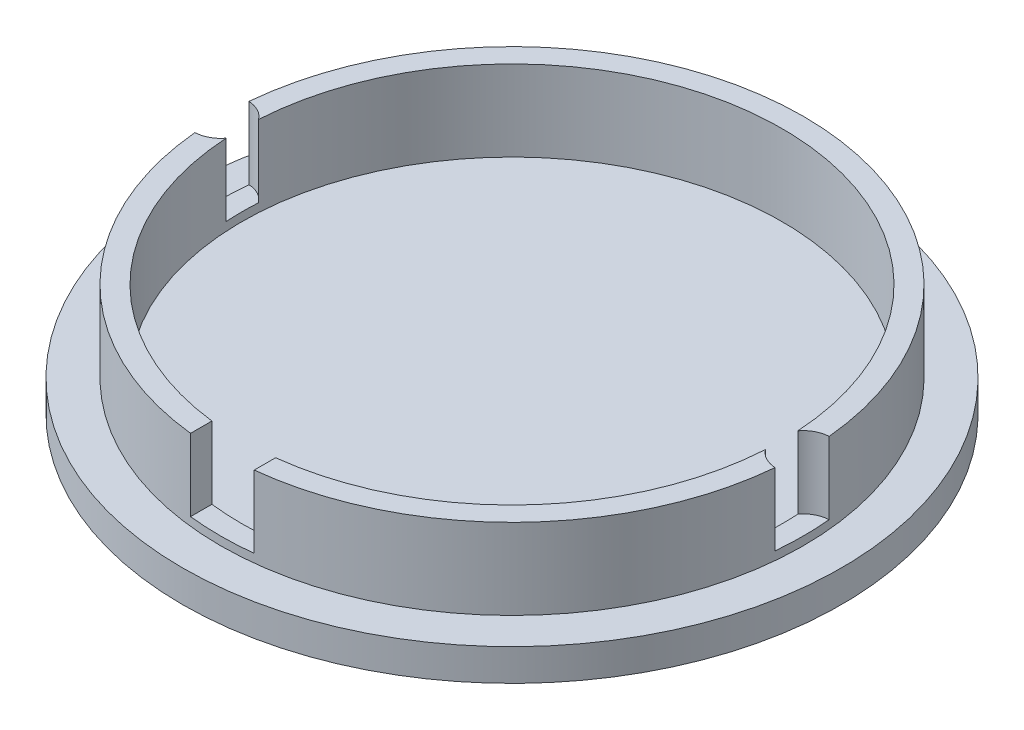
SolidWorks part; units mm, degrees
ref_plane "Front Plane" through (0, 0, 0) normal (0, 0, 1) x (1, 0, 0)
ref_plane "Top Plane" through (0, 0, 0) normal (0, 1, 0) x (1, 0, 0)
ref_plane "Right Plane" through (0, 0, 0) normal (1, 0, 0) x (0, 0, -1)
sketch "Sketch1" plane through (0, 0, 0) normal (0, 1, 0) x (1, 0, 0)
  circle A0 centre (0, 0) radius 31.06
  dimension "D1" = 62.12
extrude "Boss-Extrude1" add sketch "Sketch1" along normal blind 3
sketch "Sketch2" plane through (0, 3, 0) normal (0, 1, 0) x (1, 0, 0)
  circle A0 centre (0, 0) radius 27.46
  circle A1 centre (0, 0) radius 25.46
  circle A2 centre (0, 0) radius 31.06 construction
  dimension "D1" = 2
  dimension "D2" = 3.6
extrude "Boss-Extrude2" add sketch "Sketch2" along normal blind 7.6
sketch "Sketch4" plane through (0, 10.6, 0) normal (0, 1, 0) x (1, 0, 0)
  arc A0 (25.4144, -1.5226) -> (27.3416, -2.5472) centre (27.46, 0) ccw
  circle A1 centre (0, 0) radius 27.46 construction
  arc A2 (-27.3416, -2.5472) -> (-25.4144, -1.5226) centre (-27.46, 0) ccw
  circle A3 centre (0, 0) radius 25.46 construction
  arc A4 (-25.4144, 1.5226) -> (-25.4144, -1.5226) centre (0, 0) ccw
  arc A5 (-27.3416, 2.5472) -> (-27.3416, -2.5472) centre (0, 0) ccw
  arc A6 (25.4144, -1.5226) -> (25.4144, 1.5226) centre (0, 0) ccw
  arc A7 (27.3416, -2.5472) -> (27.3416, 2.5472) centre (0, 0) ccw
  arc A8 (-25.4144, 1.5226) -> (-27.3416, 2.5472) centre (-27.46, 0) ccw
  arc A9 (27.3416, 2.5472) -> (25.4144, 1.5226) centre (27.46, 0) ccw
  circle M1 centre (0, 0) radius 27.46
  circle M2 centre (0, 0) radius 25.46
  dimension "D1" = 5.1
  dimension "D2" = 5.1
extrude "Cut-Extrude1" cut sketch "Sketch4" against normal blind 6.8 contours A9 A0 M1 M2 | A4 A2 A5 A8 region at (26.5014, 10.6, 0)
sketch "Sketch5" plane through (0, 10.6, 0) normal (0, 1, 0) x (1, 0, 0)
  line L0 (0, -25.46) -> (0, -27.46)
  line L1 (3, -25.2826) -> (3, -27.2956)
  line L2 (-3, -25.2826) -> (-3, -27.2956)
  line L3 (3, -25.46) -> (3, -27.46) construction
  line L4 (-3, -25.46) -> (-3, -27.46) construction
  arc A0 (-25.4144, -1.5226) -> (25.4144, -1.5226) centre (0, 0) ccw construction
  arc A1 (-27.3416, -2.5472) -> (27.3416, -2.5472) centre (0, 0) ccw construction
  arc A3 (-3, -25.2826) -> (3, -25.2826) centre (0, 0) ccw
  arc A4 (-3, -27.2956) -> (3, -27.2956) centre (0, 0) ccw
  arc M2 (-27.3416, -2.5472) -> (27.3416, -2.5472) centre (0, 0) ccw
  arc M4 (25.4144, -1.5226) -> (-25.4144, -1.5226) centre (0, 0) cw
  dimension "D1" = 3
  dimension "D2" = 3
extrude "Cut-Extrude2" cut sketch "Sketch5" against normal blind 6.8 contours L2 L0 M4 M2 | L1 L0 M4 M2 region at (1.5016, 10.6, 26.403) region at (-1.5016, 10.6, 26.403)
